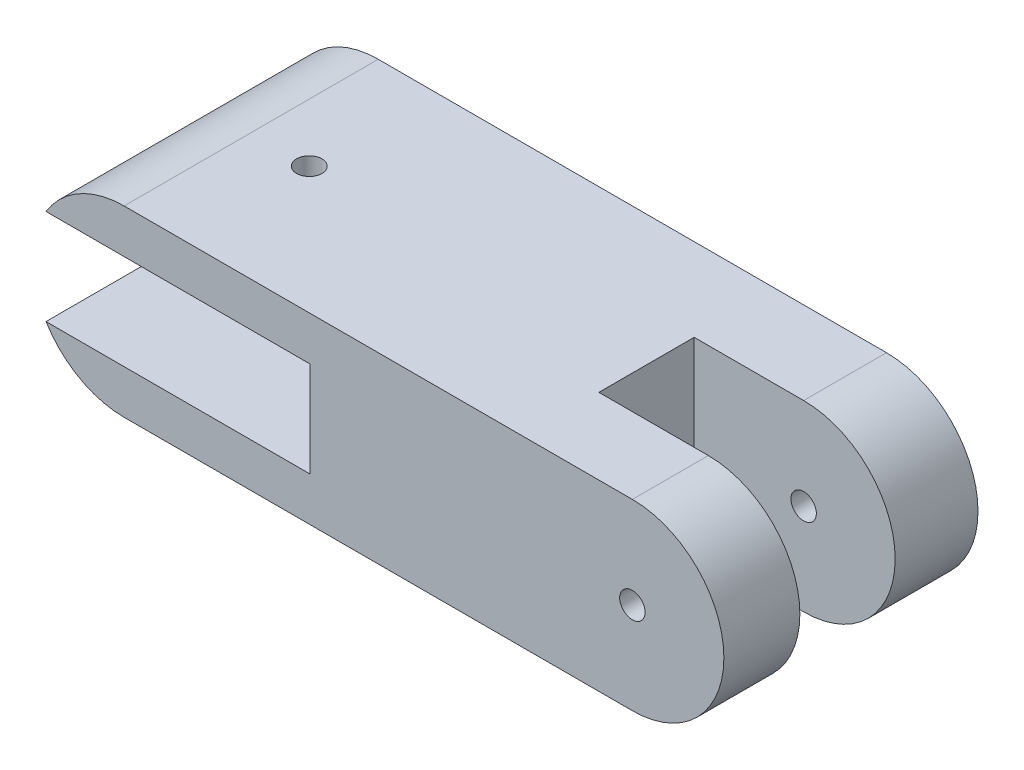
SolidWorks part; units mm, degrees
ref_plane "Plano frontal" through (0, 0, 0) normal (0, 0, 1) x (1, 0, 0)
ref_plane "Plano superior" through (0, 0, 0) normal (0, 1, 0) x (1, 0, 0)
ref_plane "Plano direito" through (0, 0, 0) normal (1, 0, 0) x (0, 0, -1)
sketch "Esboço1" plane through (0, 0, 0) normal (0, 0, 1) x (1, 0, 0)
  line L0 (-60.6729, 0) -> (-56.5569, 0) construction
  line L2 (-56.5569, 14.4058) -> (23.4431, 14.4058)
  line L4 (-56.5569, -14.4058) -> (23.4431, -14.4058)
  arc A0 (23.4431, 14.4058) -> (23.4431, -14.4058) centre (23.4431, 0) cw
  arc A1 (-56.5569, -14.4058) -> (-56.5569, 14.4058) centre (-56.5569, 0) cw
  point P0 (0, 0)
  point P4 (0, 0)
extrude "Ressalto-extrusão1" add sketch "Esboço1" along normal blind 40
sketch "Esboço2" plane through (0, 0, 40) normal (0, 0, 1) x (1, 0, 0)
  circle A0 centre (23.4431, 0) radius 2
extrude "Corte-extrusão1" cut sketch "Esboço2" against normal mid plane 80
sketch "Esboço3" plane through (0, 0, 40) normal (0, 0, 1) x (1, 0, 0)
  line L1 (-27.3239, 7.5) -> (-72.9173, 7.5)
  line L2 (-27.3239, 7.5) -> (-27.3239, -7.5)
  line L3 (-27.3239, -7.5) -> (-72.9173, -7.5)
  line L4 (-72.9173, 7.5) -> (-72.9173, -7.5)
  line L5 (-27.3239, 7.5) -> (-72.9173, -7.5) construction
  line L6 (-27.3239, -7.5) -> (-72.9173, 7.5) construction
  point P0 (-50.1206, 0)
extrude "Corte-extrusão2" cut sketch "Esboço3" against normal mid plane 80
sketch "Esboço4" plane through (0, 14.4058, 0) normal (0, 1, 0) x (1, 0, 0)
  circle A0 centre (-47.4134, -20) radius 2
extrude "Corte-extrusão3" cut sketch "Esboço4" against normal mid plane 80
sketch "Esboço6" plane through (0, 14.4058, 0) normal (0, 1, 0) x (1, 0, 0)
  line L1 (6.213, -13.0405) -> (43.9148, -13.0405)
  line L2 (6.213, -13.0405) -> (6.213, -28.0405)
  line L3 (6.213, -28.0405) -> (43.9148, -28.0405)
  line L4 (43.9148, -13.0405) -> (43.9148, -28.0405)
  point P0 (0, -20.5405)
extrude "Corte-extrusão5" cut sketch "Esboço6" against normal mid plane 125
